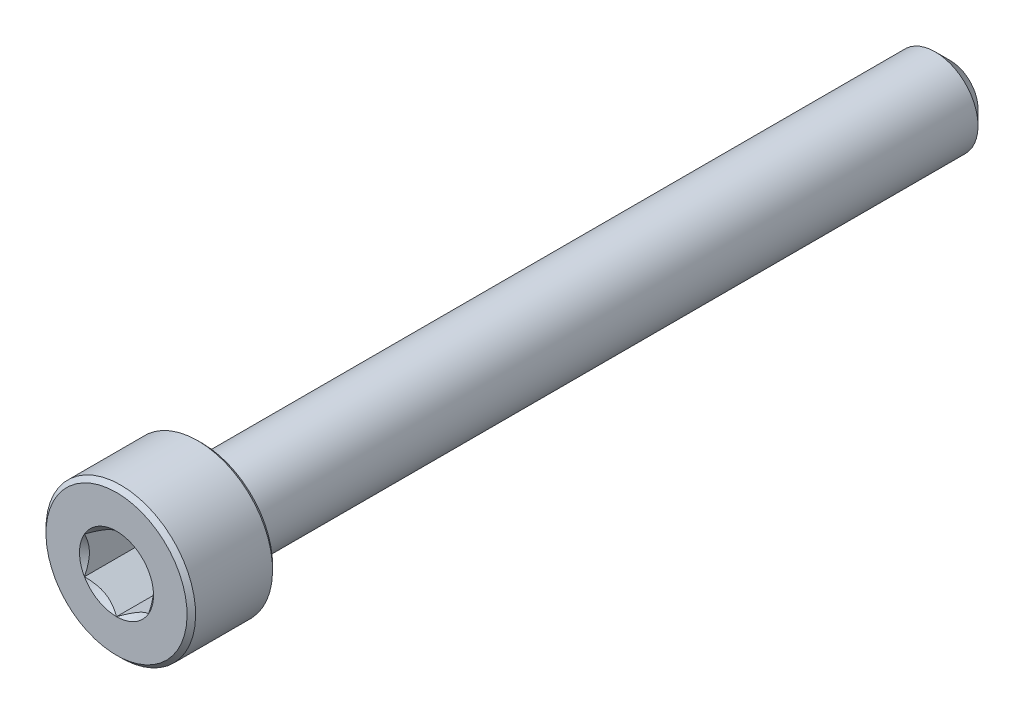
SolidWorks part; units mm, degrees
material "Plain Carbon Steel"
ref_plane "Front Plane" through (0, 0, 0) normal (0, 0, 1) x (1, 0, 0)
ref_plane "Top Plane" through (0, 0, 0) normal (0, 1, 0) x (1, 0, 0)
ref_plane "Right Plane" through (0, 0, 0) normal (1, 0, 0) x (0, 0, -1)
sketch "Sketch1" plane through (0, 0, 0) normal (1, 0, 0) x (0, 0, -1)
  line L0 (-19.5, 0) -> (19.5, 0) construction
  line L1 (19.5, 0) -> (19.5, 1.3) construction
  line L2 (19.5, 1.3) -> (18.8, 2) construction
  line L3 (18.8, 2) -> (18.975, 2) construction
  line L4 (18.975, 2) -> (-15.5, 2) construction
  line L5 (-15.5, 2) -> (-15.5, 3.5) construction
  line L6 (-15.5, 3.5) -> (-19.5, 3.5) construction
  line L7 (-19.5, 3.5) -> (-19.5, 0) construction
  line L8 (19.5, 1.3) -> (19.5, 2) construction
  line L9 (19.4563, 2.0758) -> (19.8063, 1.4696) construction
  line L10 (19.8063, 1.4696) -> (20.1563, 2.0758) construction
  line L11 (20.1563, 2.0758) -> (19.4563, 2.0758) construction
  line L12 (19.8063, 2.0758) -> (19.8063, 2) construction
  line L13 (19.8063, 1.4696) -> (19.8063, 1.5453) construction
  line L14 (19.7625, 1.5453) -> (19.85, 1.5453) construction
  line L15 (19.5, 2) -> (20.1125, 2) construction
  line L16 (19.4781, 2.0379) -> (20.1344, 2.0379) construction
  line L17 (19.5, 0) -> (19.5, -2) construction
  line L18 (-15.7, 3.5) -> (-15.5, 3.3) construction
  line L19 (-19.3, 3.5) -> (-19.5, 3.3) construction
  line L20 (-15.5, 2) -> (-15.5, 0) construction
  line L21 (-15.5, 1) -> (-3.8333, 1) construction
  line L22 (-3.8333, 1) -> (7.8333, 1) construction
  line L23 (7.8333, 1) -> (19.5, 1) construction
  line L24 (-3.8333, 1) -> (-3.8333, 2) construction
  line L25 (-3.8333, 2) -> (-3.8333, 3.5) construction
  line L26 (7.8333, 1) -> (7.8333, 3.5) construction
  point P0 (-19.5, 1.5)
  point P3 (17.75, 2)
  point P4 (0, 0)
  point P18 (7.8333, 2)
  point P22 (19.8063, 1.5453)
  point P24 (18.975, 2)
  point P25 (19.8063, 2)
  point P28 (19.8063, 2.0379)
  point P29 (17.75, -2)
  point P30 (-3.8333, 2)
  point P31 (-17.5, 3.5)
  point P37 (-16.2, 3.5)
  point P38 (-19.2, 3.5)
  point P45 (-3.8333, 1)
  point P46 (7.8333, 1)
  dimension "D1" = 45
  dimension "D2" = 0.0875
  dimension "D3" = 0.7
  dimension "D7" = 0.2
  dimension "D8" = 0.2
  dimension "D9" = 0.2
  dimension "D10" = 0.1
  dimension "D11" = 0.5
  dimension "Drive Size" = 3
  dimension "Head Diameter" = 7
  dimension "Head Height" = 4
  dimension "Thread Pitch" = 0.7
  dimension "Thread Major Diameter" = 4
  dimension "Length" = 35
  dimension "D12" = 0.525
  dimension "D4" = 1.75
sketch "Sketch2" plane through (0, 0, 0) normal (1, 0, 0) x (0, 0, -1)
  line L0 (-19.5, 0) -> (-19.5, 3.3)
  line L1 (-19.3, 3.5) -> (-15.7, 3.5)
  line L2 (-15.5, 3.3) -> (-15.5, 2)
  line L3 (-15.5, 2) -> (18.8, 2)
  line L4 (18.8, 2) -> (19.5, 1.3)
  line L5 (19.5, 1.3) -> (19.5, 0)
  line L6 (-15.7, 3.5) -> (-15.5, 3.3) construction
  line L7 (19.5, 0) -> (-19.5, 0)
  line L8 (-19.3, 3.5) -> (-19.5, 3.3) construction
  line L9 (-15.7, 3.5) -> (-15.5, 3.3)
  line L10 (-19.3, 3.5) -> (-19.5, 3.3)
revolve "Revolve1" add sketch "Sketch2" angle 360 about L7
sketch "Sketch3" plane through (0, 0, 19.5) normal (0, 0, 1) x (1, 0, 0)
  line L1 (1.5, -0.866) -> (1.5, 0.866)
  line L2 (1.5, 0.866) -> (0, 1.7321)
  line L3 (0, 1.7321) -> (-1.5, 0.866)
  line L4 (-1.5, 0.866) -> (-1.5, -0.866)
  line L5 (-1.5, -0.866) -> (0, -1.7321)
  line L6 (0, -1.7321) -> (1.5, -0.866)
  circle A0 centre (0, 0) radius 1.5 construction
extrude "Cut-Extrude1" cut sketch "Sketch3" against normal offset from surface (3 mm away) 1 up to face at (0, 3.3, 15.5)
sketch "Sketch4" plane through (0, 0, 19.5) normal (0, 0, 1) x (1, 0, 0)
  circle A0 centre (0, 0) radius 1.7321
extrude "Cut-Extrude2" cut sketch "Sketch4" against normal up to vertex (2 mm away) draft 45 up to point (0, 3.5, 17.5)
ref_plane "Plane1" [suppressed] through (0, 0, -18.975) normal (0, 0, 1) x (1, 0, 0)
split "Split1" [suppressed] bodies to split 106
sketch "Sketch6" [suppressed] plane through (0, 0, -19.5) normal (0, 0, -1) x (-1, 0, 0)
  circle A0 centre (0, 0) radius 2
curve "Helix/Spiral1" [suppressed] pitch 0.7 height 35.805 turns 51.15
sketch "Sketch7" [suppressed] plane through (0, 0, 0) normal (1, 0, 0) x (0, 0, -1)
  line L0 (19.4781, 2.0379) -> (20.1344, 2.0379)
  line L1 (20.1344, 2.0379) -> (19.85, 1.5453)
  line L2 (19.85, 1.5453) -> (19.7625, 1.5453)
  line L3 (19.7625, 1.5453) -> (19.4781, 2.0379)
sweep "Cut-Sweep1" [suppressed] cut profiles "Sketch7" path "Helix/Spiral1"
sketch "Sketch8" [suppressed] plane through (0, 0, 15.5) normal (0, 0, -1) x (-1, 0, 0)
  circle A0 centre (0, 0) radius 2
extrude "Boss-Extrude1" [suppressed] add sketch "Sketch8" along normal through all draft 45
equation "\"D2@Sketch1\" = \"Thread Pitch@Sketch1\" / 8"
equation "\"D3@Sketch1\"= \"Thread Pitch@Sketch1\""
equation "\"D4@Helix/Spiral1\" = \"Thread Pitch@Sketch1\""
equation "\"D7@Sketch1\" = \"Head Height@Sketch1\" * .05"
equation "\"D8@Sketch1\"=\"D7@Sketch1\""
equation "\"D9@Sketch1\"=\"D7@Sketch1\""
equation "\"D10@Sketch1\"=\"D7@Sketch1\"/2"
equation "\"D11@Sketch1\"=\"D10@Sketch1\"*5"
equation "\"D4@Sketch1\"=\"Thread Pitch@Sketch1\"*2.5"
equation "\"D12@Sketch1\"=\"Thread Pitch@Sketch1\"*.75"
